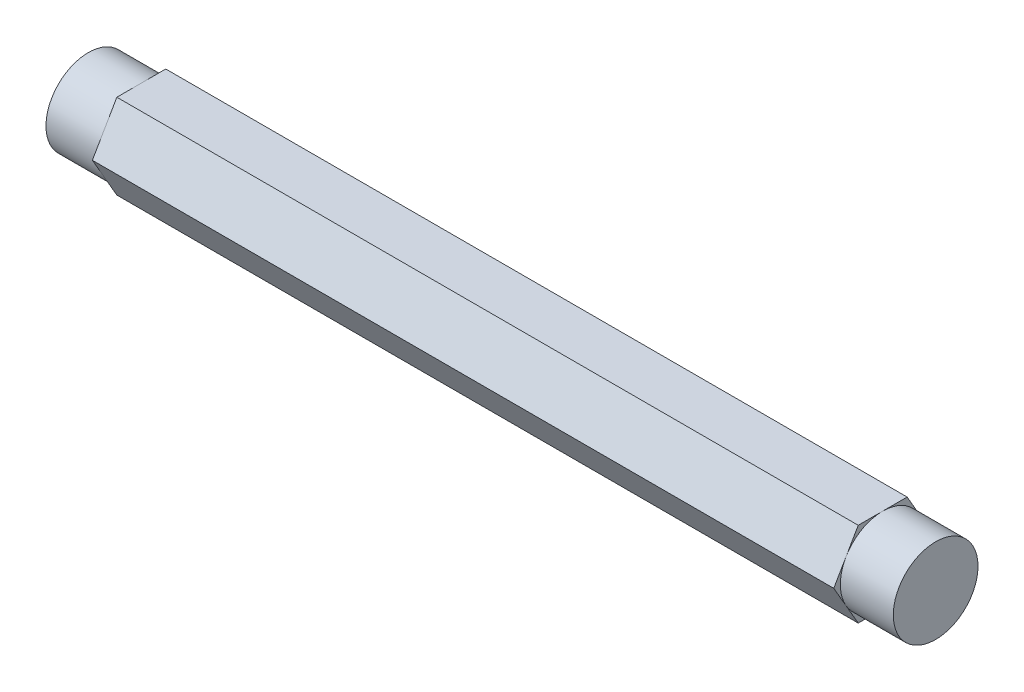
SolidWorks part; units mm, degrees
material "6061-T6 (SS)"
ref_plane "Front Plane" through (0, 0, 0) normal (0, 0, 1) x (1, 0, 0)
ref_plane "Top Plane" through (0, 0, 0) normal (0, 1, 0) x (1, 0, 0)
ref_plane "Right Plane" through (0, 0, 0) normal (1, 0, 0) x (0, 0, -1)
sketch "Sketch2" plane through (0, 0, 0) normal (1, 0, 0) x (0, 0, -1)
  line L1 (7.3323, 0) -> (3.6662, 6.35)
  line L2 (3.6662, 6.35) -> (-3.6662, 6.35)
  line L3 (-3.6662, 6.35) -> (-7.3323, 0)
  line L4 (-7.3323, 0) -> (-3.6662, -6.35)
  line L5 (-3.6662, -6.35) -> (3.6662, -6.35)
  line L6 (3.6662, -6.35) -> (7.3323, 0)
  circle A0 centre (0, 0) radius 6.35 construction
  dimension "D1" = 12.7
extrude "Boss-Extrude1" add sketch "Sketch2" along normal mid plane 127
sketch "Sketch3" plane through (63.5, 0, 0) normal (1, 0, 0) x (0, 0, -1)
  circle A0 centre (0, 0) radius 6.35
  dimension "D1" = 12.7
extrude "Cut-Extrude-Thin1" cut sketch "Sketch3" against normal blind 7.9375 thin thin type one direction wall 2.54
mirror "Mirror1" about plane through (0, 0, 0) normal (1, 0, 0) of "Cut-Extrude-Thin1"
